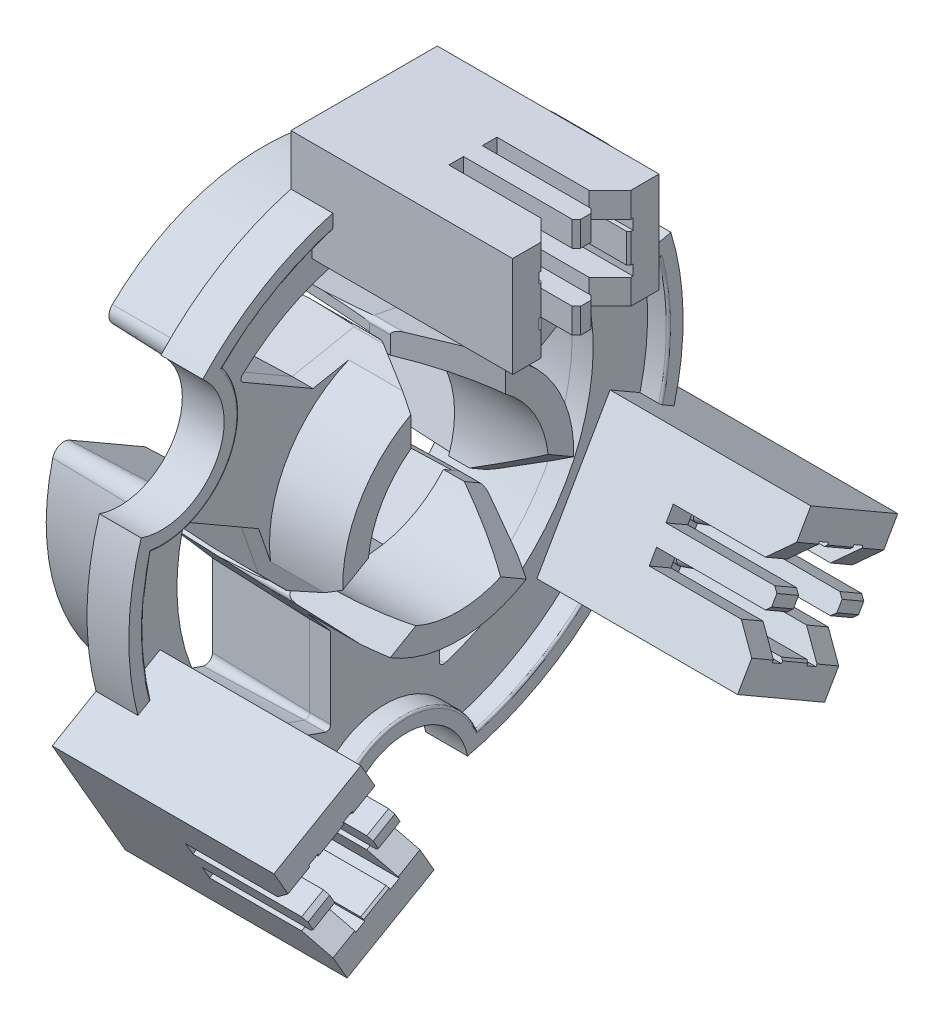
SolidWorks part; units mm, degrees
ref_plane "前视基准面" through (0, 0, 0) normal (0, 0, 1) x (1, 0, 0)
ref_plane "上视基准面" through (0, 0, 0) normal (0, 1, 0) x (1, 0, 0)
ref_plane "右视基准面" through (0, 0, 0) normal (1, 0, 0) x (0, 0, -1)
sketch "草图1" plane through (0, 0, 0) normal (0, 0, 1) x (1, 0, 0)
  line L0 (-12.1146, 0) -> (14.7387, 0) construction
  line L1 (0, 16.6473) -> (0, -11.3565) construction
  line L2 (0, 13.25) -> (1, 13.25)
  line L5 (1, 13.25) -> (1, 4.1)
  line L6 (1, 4.1) -> (0, 4.1)
  line L7 (0, 4.1) -> (0, 13.25)
  dimension "D1" = 26.5
  dimension "D2" = 1
  dimension "D3" = 8.2
revolve "旋转1" add sketch "草图1" angle 360 about L0
sketch "草图20" plane through (0, 0, 0) normal (-1, 0, 0) x (0, 0, 1)
  line L0 (-18.536, 0) -> (19.9157, 0) construction
  line L1 (0, 14.2878) -> (0, -15.5223) construction
  line L2 (9.1799, -5.3) -> (-15.6646, 9.0439) construction
  line L3 (0, 0) -> (15.9538, 9.2109) construction
  line L4 (0, 0) -> (-14.705, -8.4899) construction
  line L6 (0.9543, 0.0929) -> (0.325, -0.9971) construction
  circle A0 centre (0, 0) radius 10.6 construction
  arc A1 (0, 4.5642) -> (-3.9527, -2.2821) centre (0.6755, -0.39) ccw
  arc A2 (3.9527, -2.2821) -> (0, 4.5642) centre (-0.6755, -0.39) ccw
  arc A3 (-3.9527, -2.2821) -> (3.9527, -2.2821) centre (0, 0.78) ccw
  point P16 (0.6755, -0.39)
  point P26 (0, 0)
  dimension "D3" = 21.2
  dimension "D6" = 10
  dimension "D1" = 60
  dimension "D2" = 60
  dimension "D4" = 0.78
  dimension "D5" = 60
  dimension "D7" = 3
extrude "切除-拉伸7" cut sketch "草图20" against normal blind 10
sketch "草图2" plane through (0, 0, 0) normal (-1, 0, 0) x (0, 0, 1)
  line L0 (-16.221, 0) -> (19.4228, 0) construction
  line L1 (0, 16.0936) -> (0, -16.7209) construction
  line L2 (0, 0) -> (-14.0552, 8.1148) construction
  line L3 (0, 0) -> (15.0558, 8.6925) construction
  line L4 (-7.2036, 6.4684) -> (-3.5494, 4.3587)
  line L5 (-3.5494, 4.3587) -> (-0.25, 5)
  line L6 (-0.25, 5.6112) -> (-0.25, 5)
  line L7 (0.25, 5.6112) -> (0.25, 5)
  line L8 (3.5494, 4.3587) -> (0.25, 5)
  line L9 (7.2036, 6.4684) -> (3.5494, 4.3587)
  line L10 (3.4437, 4.9904) -> (0.85, 5.4946) construction
  line L11 (3.4437, 4.9904) -> (0.25, 5.6112)
  line L12 (6.7881, 6.9213) -> (3.4437, 4.9904)
  line L13 (-6.7881, 6.9213) -> (-3.4437, 4.9904)
  line L14 (-3.4437, 4.9904) -> (-0.25, 5.6112)
  line L15 (-3.4437, 4.9904) -> (-0.85, 5.4946) construction
  line L16 (-0.85, 6.5945) -> (-0.85, 5.4946) construction
  line L17 (0.85, 6.3945) -> (0.85, 5.4946) construction
  line L18 (-6.9036, 6.988) -> (-3.4437, 4.9904) construction
  line L19 (0.25, 6.3945) -> (0.25, 5) construction
  line L20 (-0.25, 6.5945) -> (-0.25, 5) construction
  line L21 (6.9036, 6.988) -> (3.4437, 4.9904) construction
  arc A0 (7.3407, 7.5774) -> (-7.3407, 7.5774) centre (0, 0) ccw
  arc A3 (7.2036, 6.4684) -> (7.3407, 7.5774) centre (6.8536, 7.0746) ccw
  arc A4 (-7.2036, 6.4684) -> (-7.3407, 7.5774) centre (-6.8536, 7.0746) cw
  arc A6 (6.8253, 7.24) -> (-6.8253, 7.24) centre (0, 0) ccw
  arc A7 (6.8253, 7.24) -> (6.7881, 6.9213) centre (6.6881, 7.0945) cw
  arc A8 (6.9232, 7.1465) -> (-6.9232, 7.1465) centre (0, 0) ccw construction
  arc A9 (-6.7881, 6.9213) -> (-6.8253, 7.24) centre (-6.6881, 7.0945) cw
  arc A10 (-6.9036, 6.988) -> (-6.9232, 7.1465) centre (-6.8536, 7.0746) cw construction
  arc A11 (6.9036, 6.988) -> (6.9232, 7.1465) centre (6.8536, 7.0746) ccw construction
  dimension "D1" = 21.1
  dimension "D8" = 0.7
  dimension "D11" = 0.2
  dimension "D12" = 0.2
  dimension "D7" = 5
  dimension "D2" = 60
  dimension "D3" = 60
  dimension "D4" = 2
  dimension "D5" = 139
  dimension "D6" = 0.25
  dimension "D9" = 2
  dimension "D13" = 0.6
  dimension "D10" = 0.6
extrude "凸台-拉伸1" add sketch "草图2" along normal blind 4.8 draft 1.8
pattern_circular "阵列(圆周)1" count 3 over 360 about axis through (-12.1146, 0, 0) along (-1, 0, 0) of "凸台-拉伸1" reverse direction yes
sketch "草图3" plane through (0, 0, 0) normal (-1, 0, 0) x (0, 0, 1)
  line L0 (-15.829, 0) -> (17.3645, 0) construction
  line L1 (0, 16.96) -> (0, -16.96) construction
  line L20 (6.7881, 6.9213) -> (3.4437, 4.9904) construction
  line L21 (-3.4437, 4.9904) -> (-6.7881, 6.9213) construction
  line L22 (-0.25, 5) -> (-0.25, 5.6112) construction
  line L23 (-0.25, 5.6112) -> (-3.4437, 4.9904) construction
  line L24 (6.7881, 6.9213) -> (3.4437, 4.9904)
  line L25 (-3.4437, 4.9904) -> (-6.7881, 6.9213)
  line L26 (-0.25, 4.0924) -> (-0.25, 5.3686)
  line L27 (-0.4882, 5.5649) -> (-3.4437, 4.9904)
  line L28 (0.25, 5.6112) -> (0.25, 5) construction
  line L29 (3.4437, 4.9904) -> (0.25, 5.6112) construction
  line L30 (0.25, 5.3686) -> (0.25, 4.0924)
  line L31 (3.4437, 4.9904) -> (0.4882, 5.5649)
  arc A8 (6.7881, 6.9213) -> (6.8253, 7.24) centre (6.6881, 7.0945) ccw construction
  arc A9 (6.7881, 6.9213) -> (6.8253, 7.24) centre (6.6881, 7.0945) ccw
  arc A12 (6.8253, 7.24) -> (-6.8253, 7.24) centre (0, 0) ccw construction
  arc A13 (-6.8253, 7.24) -> (-6.7881, 6.9213) centre (-6.6881, 7.0945) ccw construction
  arc A14 (6.8253, 7.24) -> (-6.8253, 7.24) centre (0, 0) ccw
  arc A15 (-6.8253, 7.24) -> (-6.7881, 6.9213) centre (-6.6881, 7.0945) ccw
  arc A16 (0.4882, 5.5649) -> (0.25, 5.3686) centre (0.45, 5.3686) ccw
  arc A17 (-0.25, 5.3686) -> (-0.4882, 5.5649) centre (-0.45, 5.3686) ccw
  arc A18 (0.25, 4.0924) -> (-0.25, 4.0924) centre (0, 0) ccw
  dimension "D1" = 8.2
  dimension "D2" = 0.2
extrude "切除-拉伸1" cut sketch "草图3" against normal mid plane 14.8
pattern_circular "阵列(圆周)2" count 3 over 360 about axis through (0, 0, 0) along (-1, 0, 0) of "切除-拉伸1"
sketch "草图21" plane through (1, 0, 0) normal (1, 0, 0) x (0, 0, -1)
  line L0 (-0.25, 4.5236) -> (-0.25, 5.3686) construction
  line L1 (-0.25, 4.5236) -> (-0.25, 5.3686)
  line L2 (-4.7744, -2.4678) -> (-4.0426, -2.0453) construction
  line L3 (-4.7744, -2.4678) -> (-4.0426, -2.0453)
  line L6 (-0.4882, 5.5649) -> (-3.4437, 4.9904) construction
  line L7 (-0.4882, 5.5649) -> (-1.7335, 5.3229)
  line L8 (-6.0437, 0.4871) -> (-5.0635, -2.3597) construction
  line L9 (-5.4765, -1.1602) -> (-5.0635, -2.3597)
  arc A0 (-0.25, 4.5236) -> (-4.0426, -2.0453) centre (0.6755, -0.39) ccw construction
  arc A1 (-0.25, 4.5236) -> (-4.0426, -2.0453) centre (0.6755, -0.39) ccw
  arc A3 (-1.7335, 5.3229) -> (-5.4765, -1.1602) centre (0.6755, -0.39) ccw
  arc A11 (-0.25, 5.3686) -> (-0.4882, 5.5649) centre (-0.45, 5.3686) ccw construction
  arc A12 (-0.25, 5.3686) -> (-0.4882, 5.5649) centre (-0.45, 5.3686) ccw
  arc A13 (-5.0635, -2.3597) -> (-4.7744, -2.4678) centre (-4.8744, -2.2946) ccw construction
  arc A16 (-5.0635, -2.3597) -> (-4.7744, -2.4678) centre (-4.8744, -2.2946) ccw
  point P14 (-1.5205, 5.4081)
  point P15 (0.6755, -0.39)
  point P16 (-5.4438, -1.3872)
  dimension "D1" = 12.4
extrude "凸台-拉伸5" add sketch "草图21" along normal blind 3.5
pattern_circular "阵列(圆周)8" count 3 over 360 about axis through (-12.1146, 0, 0) along (-1, 0, 0) of "凸台-拉伸5"
sketch "草图5" plane through (0, 0, 0) normal (0, 1, 0) x (1, 0, 0)
  line L0 (-10.3596, 0) -> (16.169, 0) construction
  line L1 (0, -13.3133) -> (0, 14.2281) construction
  line L2 (1, -9.5779) -> (1, 3.3379) construction
  line L3 (1, -0.25) -> (4.8245, -2.4581)
  line L4 (1, 0.25) -> (4.8245, 2.4581)
  line L5 (1, -0.25) -> (1, 0.25)
  line L6 (4.8245, -2.4581) -> (4.8245, 2.4581)
  dimension "D1" = 1
  dimension "D2" = 0.25
  dimension "D3" = 30
extrude "切除-拉伸2" cut sketch "草图5" along normal blind 6.8 contours L3 L6 L4 L5
pattern_circular "阵列(圆周)3" count 3 over 360 about axis through (-12.1146, 0, 0) along (-1, 0, 0) of "切除-拉伸2"
sketch "草图7" plane through (0, 0, 0) normal (-1, 0, 0) x (0, 0, 1)
  line L0 (-14.5222, 0) -> (14.1954, 0) construction
  line L1 (0, 13.4113) -> (0, -13.444) construction
  line L2 (0, 0) -> (-14.3255, 8.2708) construction
  circle A0 centre (0, 0) radius 13.5 construction
  circle A1 centre (-11.6913, 6.75) radius 3
  dimension "D2" = 27
  dimension "D3" = 6
  dimension "D1" = 60
extrude "切除-拉伸4" cut sketch "草图7" against normal blind 6.8 contours A1
pattern_circular "阵列(圆周)5" count 3 over 360 about axis through (-12.1146, 0, 0) along (-1, 0, 0) of "切除-拉伸4"
sketch "草图9" plane through (1, 0, 0) normal (1, 0, 0) x (0, 0, -1)
  arc A0 (9.7166, 9.0084) -> (12.6598, 3.9106) centre (11.6913, 6.75) ccw construction
  arc A1 (2.9432, -12.919) -> (12.6598, 3.9106) centre (0, 0) ccw construction
  arc A2 (2.9432, -12.919) -> (-2.9432, -12.919) centre (0, -13.5) ccw construction
  arc A3 (-12.6598, 3.9106) -> (-2.9432, -12.919) centre (0, 0) ccw construction
  arc A4 (-12.6598, 3.9106) -> (-9.7166, 9.0084) centre (-11.6913, 6.75) ccw construction
  arc A5 (9.7166, 9.0084) -> (-9.7166, 9.0084) centre (0, 0) ccw construction
  arc A6 (9.7166, 9.0084) -> (12.6598, 3.9106) centre (11.6913, 6.75) ccw
  arc A7 (2.9432, -12.919) -> (12.6598, 3.9106) centre (0, 0) ccw
  arc A8 (2.9432, -12.919) -> (-2.9432, -12.919) centre (0, -13.5) ccw
  arc A9 (-12.6598, 3.9106) -> (-2.9432, -12.919) centre (0, 0) ccw
  arc A10 (-12.6598, 3.9106) -> (-9.7166, 9.0084) centre (-11.6913, 6.75) ccw
  arc A11 (9.7166, 9.0084) -> (-9.7166, 9.0084) centre (0, 0) ccw
  arc A12 (8.7509, 8.9958) -> (-8.7509, 8.9958) centre (0, 0) ccw
  arc A13 (-12.166, 3.0806) -> (-8.7509, 8.9958) centre (-11.6913, 6.75) ccw
  arc A14 (-12.166, 3.0806) -> (-3.4152, -12.0764) centre (0, 0) ccw
  arc A15 (3.4152, -12.0764) -> (-3.4152, -12.0764) centre (0, -13.5) ccw
  arc A16 (3.4152, -12.0764) -> (12.166, 3.0806) centre (0, 0) ccw
  arc A17 (8.7509, 8.9958) -> (12.166, 3.0806) centre (11.6913, 6.75) ccw
  dimension "D2" = 12.55
  dimension "D1" = 0.7
extrude "凸台-拉伸2" add sketch "草图9" along normal blind 1
fillet "圆角5" radius 0.1 6 edges at (2, 4.9, -8.487) (2, -6.275, -10.8686) (2, -9.8, 0) (2, -6.275, 10.8686) (2, 4.9, 8.487) (2, 12.55, 0)
sketch "草图10" plane through (0, 0, 0) normal (-1, 0, 0) x (0, 0, 1)
  line L0 (-17.635, 0) -> (18.1303, 0) construction
  line L1 (0, 19.88) -> (0, -18.2041) construction
  line L2 (3.5, 15.2) -> (-3.5, 15.2)
  line L3 (-3.5, 15.2) -> (-3.5, 10.4)
  line L4 (-3.5, 10.4) -> (3.5, 10.4)
  line L5 (3.5, 15.2) -> (3.5, 10.4)
  point P10 (0, 10.4)
  point P11 (0, 15.2)
  dimension "D1" = 7
  dimension "D2" = 4.8
  dimension "D3" = 15.2
extrude "凸台-拉伸3" add sketch "草图10" against normal blind 10.6 contours L2 L3 L4 L5
sketch "草图12" plane through (10.6, 0, 0) normal (1, 0, 0) x (0, 0, -1)
  line L0 (-5.7935, 12.8) -> (6.2031, 12.8) construction
  line L1 (0, 15.8559) -> (0, 9.2714) construction
  line L2 (-3.5, 15.2) -> (3.5, 15.2) construction
  line L3 (2.25, 14) -> (-2.25, 14)
  line L4 (-2.25, 14) -> (-2.25, 13.5)
  line L5 (-2.25, 13.5) -> (-2.05, 13.5)
  line L6 (-2.05, 13.5) -> (-2.05, 12.1)
  line L7 (-2.25, 12.1) -> (-2.05, 12.1)
  line L8 (-2.25, 11.6) -> (-2.25, 12.1)
  line L9 (2.25, 11.6) -> (-2.25, 11.6)
  line L10 (2.25, 11.6) -> (2.25, 12.1)
  line L11 (2.25, 12.1) -> (2.05, 12.1)
  line L12 (2.05, 13.5) -> (2.05, 12.1)
  line L13 (2.25, 13.5) -> (2.05, 13.5)
  line L14 (2.25, 14) -> (2.25, 13.5)
  point P7 (2.05, 12.8)
  point P13 (-2.05, 12.8)
  point P17 (0, 11.6)
  point P22 (0, 14)
  dimension "D1" = 2.4
  dimension "D2" = 4.1
  dimension "D3" = 4.5
  dimension "D4" = 2.4
  dimension "D5" = 0.5
extrude "切除-拉伸5" cut sketch "草图12" against normal blind 6.8 contours L3 L4 L5 L6 L7 L8 L9 L10 L11 L12 L13 L14
sketch "草图13" plane through (3.8, 0, 0) normal (1, 0, 0) x (0, 0, -1)
  line L0 (-4.4335, 12.8) -> (4.2997, 12.8) construction
  line L1 (0, 16.082) -> (0, 8.7447) construction
  line L2 (-3.5, 15.2) -> (3.5, 15.2) construction
  circle A0 centre (-0.8, 12.8) radius 0.45
  circle A1 centre (0.8, 12.8) radius 0.45
  dimension "D2" = 0.9
  dimension "D3" = 1.6
  dimension "D1" = 2.4
extrude "凸台-拉伸4" add sketch "草图13" along normal blind 1.4
sketch "草图15" plane through (0, 15.2, 0) normal (0, 1, 0) x (1, 0, 0)
  line L0 (-7.0769, 0) -> (14.9905, 0) construction
  line L1 (10.6, 2.15) -> (9.6, 1.15)
  line L2 (10.6, -3.5) -> (10.6, 3.5) construction
  line L3 (9.6, 1.15) -> (5.2, 1.15)
  line L4 (5.2, 1.15) -> (5.2, 0.45)
  line L5 (5.2, 0.45) -> (10.6, 0.45)
  line L6 (5.2, -0.45) -> (10.6, -0.45)
  line L7 (5.2, -1.15) -> (5.2, -0.45)
  line L8 (9.6, -1.15) -> (5.2, -1.15)
  line L9 (10.6, -2.15) -> (9.6, -1.15)
  line L10 (10.6, 2.15) -> (10.6, 0.45)
  line L11 (10.6, -0.45) -> (10.6, -2.15)
  dimension "D1" = 0.7
  dimension "D2" = 0.9
  dimension "D3" = 135
  dimension "D4" = 1
  dimension "D5" = 5.4
extrude "切除-拉伸6" cut sketch "草图15" against normal blind 11.2
chamfer "倒角1" distance 0.2 angle 45 4 edges at (10.6, 11, 0.45) (10.6, 11, -0.45) (10.6, 14.6, 0.45) (10.6, 14.6, -0.45)
pattern_circular "阵列(圆周)6" count 3 over 360 about axis through (-12.1146, 0, 0) along (-1, 0, 0) of "凸台-拉伸3", "切除-拉伸5", "凸台-拉伸4", "切除-拉伸6", "倒角1"
ref_plane "基准面1" through (0, -6.4, -11.0851) normal (0, 0.5, 0.866) x (1, 0, 0)
sketch "草图16" plane through (0, -6.4, -11.0851) normal (0, 0.5, 0.866) x (1, 0, 0)
  line L0 (11.4243, 0) -> (-0.6489, 0) construction
  line L1 (10.4, 0.45) -> (5.2, 0.45) construction
  line L2 (6.2081, 0.8) -> (3.1222, 0.8) construction
  line L3 (5.2, 1.1) -> (4.7, 1.25)
  line L4 (4.7, 1.25) -> (5.2, 1.25)
  line L6 (5.2, 0.35) -> (5.2, 1.25) construction
  line L7 (5.2, 1.1) -> (5.2, 1.25)
  dimension "D1" = 0.45
  dimension "D2" = 0.8
  dimension "D3" = 0.6
  dimension "D4" = 0.5
  dimension "D5" = 0.9
revolve "切除-旋转1" cut sketch "草图16" angle 360 about L2
sketch "草图18" plane through (0, -6.4, -11.0851) normal (0, 0.5, 0.866) x (1, 0, 0)
  line L0 (12.4706, 0) -> (-1.4063, 0) construction
  line L1 (2.6031, -0.8) -> (6.4978, -0.8) construction
  line L2 (5.2, -0.5) -> (4.7, -0.35)
  line L3 (5.2, -1.25) -> (5.2, -0.35) construction
  line L4 (4.7, -0.35) -> (5.2, -0.35)
  line L5 (5.2, -0.35) -> (5.2, -0.5)
  dimension "D1" = 0.8
  dimension "D2" = 0.6
  dimension "D3" = 0.9
  dimension "D4" = 0.5
revolve "切除-旋转2" cut sketch "草图18" angle 360 about L1
pattern_circular "阵列(圆周)7" count 3 over 360 about axis through (-12.1146, 0, 0) along (-1, 0, 0) of "切除-旋转1", "切除-旋转2"
